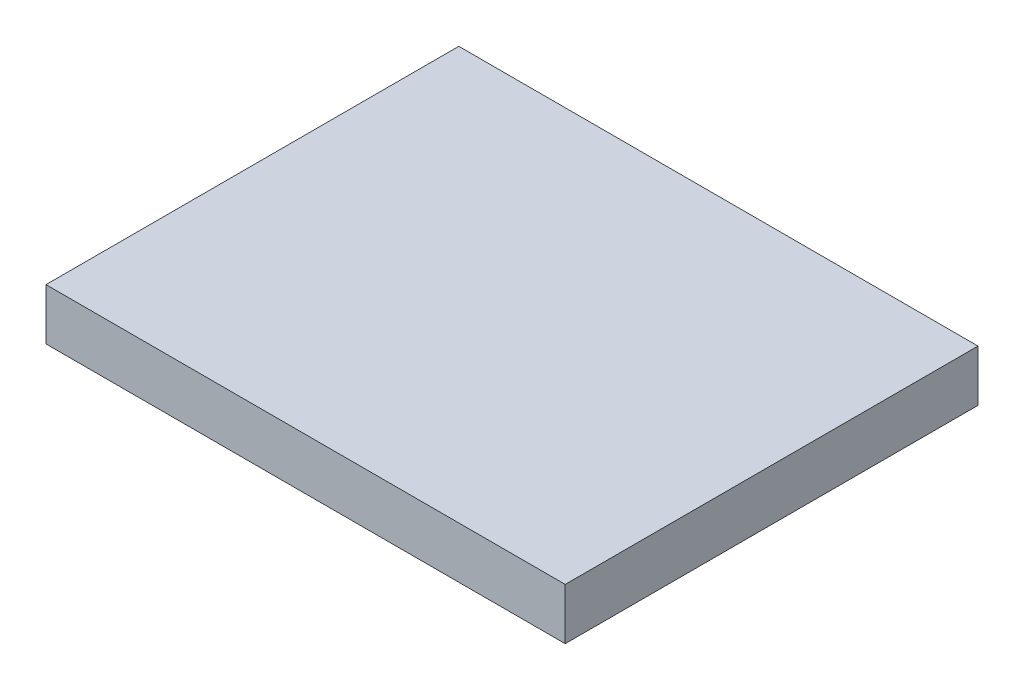
SolidWorks part; units mm, degrees
ref_plane "Front Plane" through (0, 0, 0) normal (0, 0, 1) x (1, 0, 0)
ref_plane "Top Plane" through (0, 0, 0) normal (0, 1, 0) x (1, 0, 0)
ref_plane "Right Plane" through (0, 0, 0) normal (1, 0, 0) x (0, 0, -1)
sketch "Sketch1" plane through (0, 0, 0) normal (0, 1, 0) x (1, 0, 0)
  line L1 (0, 0) -> (283, 0)
  line L2 (0, 0) -> (0, 225)
  line L3 (0, 225) -> (283, 225)
  line L4 (283, 0) -> (283, 225)
  dimension "D1" = 225
  dimension "D2" = 283
extrude "Boss-Extrude1" add sketch "Sketch1" along normal blind 28
equation "\"Length\" = 283"
equation "\"Width\" = 225"
equation "\"WallThickness\" = 12.5"
equation "\"D1@Sketch1\"=\"Width\""
equation "\"D2@Sketch1\"=\"Length\""
equation "\"UpperWaterJacketThickness\" = 28"
equation "\"D1@Boss-Extrude1\"=\"UpperWaterJacketThickness\""
